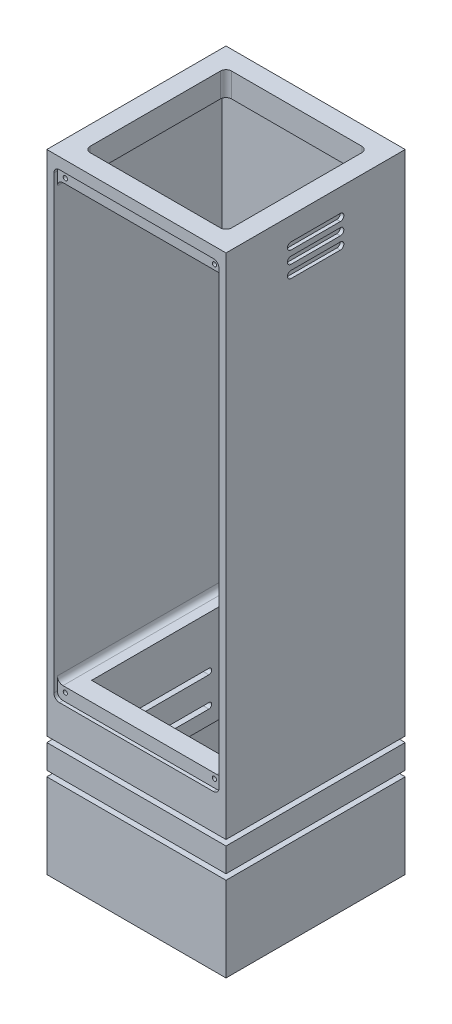
SolidWorks part; units mm, degrees
ref_plane "Front Plane" through (0, 0, 0) normal (0, 0, 1) x (1, 0, 0)
ref_plane "Top Plane" through (0, 0, 0) normal (0, 1, 0) x (1, 0, 0)
ref_plane "Right Plane" through (0, 0, 0) normal (1, 0, 0) x (0, 0, -1)
sketch "Sketch1" plane through (0, 0, 0) normal (0, 1, 0) x (1, 0, 0)
  line L0 (6.35, 44.45) -> (44.45, 44.45)
  line L1 (0, 0) -> (50.8, 0)
  line L2 (0, 0) -> (0, 50.8)
  line L3 (0, 50.8) -> (50.8, 50.8)
  line L4 (50.8, 0) -> (50.8, 50.8)
  line L5 (44.45, 6.35) -> (44.45, 44.45)
  line L6 (6.35, 6.35) -> (44.45, 6.35)
  line L7 (6.35, 6.35) -> (6.35, 44.45)
  dimension "D1" = 50.8
  dimension "D2" = 6.35
extrude "Boss-Extrude1" add sketch "Sketch1" along normal blind 178
sketch "Sketch2" plane through (0, 0, 0) normal (0, -1, 0) x (1, 0, 0)
  line L0 (47.8, -3) -> (3, -3)
  line L1 (3, -3) -> (3, -47.8)
  line L2 (3, -47.8) -> (47.8, -47.8)
  line L3 (47.8, -47.8) -> (47.8, -3)
  line L4 (6.35, -44.45) -> (44.45, -44.45)
  line L5 (6.35, -6.35) -> (6.35, -44.45)
  line L6 (44.45, -6.35) -> (6.35, -6.35)
  line L7 (44.45, -44.45) -> (44.45, -6.35)
  line L8 (6.35, -44.45) -> (44.45, -44.45)
  line L9 (6.35, -6.35) -> (6.35, -44.45)
  line L10 (44.45, -6.35) -> (6.35, -6.35)
  line L11 (44.45, -44.45) -> (44.45, -6.35)
  line L12 (0, -50.8) -> (0, 0) construction
  dimension "D2" = 3
  dimension "D1" = 0
extrude "Cut-Extrude1" cut sketch "Sketch2" against normal blind 20
sketch "Sketch3" plane through (0, 0, 0) normal (0, 0, 1) x (1, 0, 0)
  line L0 (0, 0) -> (50.8, 0) construction
  line L1 (2, 171.15) -> (48.8, 171.15)
  line L2 (2, 171.15) -> (2, 47.675)
  line L3 (2, 47.675) -> (48.8, 47.675)
  line L4 (48.8, 171.15) -> (48.8, 47.675)
  line L5 (0, 178) -> (0, 0) construction
  line L6 (50.8, 178) -> (50.8, 0) construction
  line L7 (0, 178) -> (50.8, 178) construction
  dimension "D1" = 47.675
  dimension "D2" = 2
  dimension "D3" = 2
  dimension "D4" = 6.85
extrude "Cut-Extrude2" cut sketch "Sketch3" against normal blind 47.625
sketch "Sketch4" plane through (0, 0, 0) normal (0, 0, 1) x (1, 0, 0)
  line L0 (0, 178) -> (0, 0) construction
  line L2 (0, 40) -> (0, 24)
  line L3 (0, 24) -> (50.8, 24)
  line L4 (50.8, 40) -> (50.8, 24)
  line L5 (50.8, 178) -> (50.8, 0) construction
  line L6 (0, 0) -> (50.8, 0) construction
  line L10 (0, 40) -> (50.8, 40)
  point P0 (50.8, 39.7289)
  point P10 (0, 39.7848)
  dimension "D1" = 24
  dimension "D2" = 16
extrude "Cut-Extrude3" [suppressed] cut sketch "Sketch4" against normal blind 3.175
sketch "Sketch5" [suppressed] plane through (0, 0, 0) normal (0, 0, 1) x (1, 0, 0)
  line L0 (50.8, 40) -> (0, 40) construction
  line L3 (0, 40) -> (3, 40)
  line L5 (0, 24) -> (50.8, 24) construction
  line L8 (0, 24) -> (3, 24)
  line L10 (0, 40) -> (0, 24)
  line L11 (3, 40) -> (3, 24)
  line L12 (0, 24) -> (0, 0) construction
  point P0 (0, 24)
  dimension "D1" = 3
extrude "Cut-Extrude4" [suppressed] cut sketch "Sketch5" against normal through all
ref_plane "Plane1" through (0, 0, -25.4) normal (0, 0, 1) x (1, 0, 0)
ref_plane "Plane2" through (25.4, 0, 0) normal (-1, 0, 0) x (0, 0, 1)
sketch "Sketch6" plane through (0, 0, 0) normal (-1, 0, 0) x (0, 0, 1)
  line L0 (-32.4, 170.5) -> (-18.4, 170.5) construction
  line L1 (-32.4, 171.5) -> (-18.4, 171.5)
  line L2 (-32.4, 169.5) -> (-18.4, 169.5)
  line L3 (-32.4, 167) -> (-18.4, 167) construction
  line L4 (-32.4, 168) -> (-18.4, 168)
  line L5 (-32.4, 166) -> (-18.4, 166)
  line L6 (-32.4, 163.5) -> (-18.4, 163.5) construction
  line L9 (-32.4, 164.5) -> (-18.4, 164.5)
  line L10 (-32.4, 162.5) -> (-18.4, 162.5)
  line L11 (-25.4, 170.5) -> (-25.4, 167) construction
  line L12 (-25.4, 167) -> (-25.4, 163.5) construction
  line L13 (-25.4, 170.5) -> (-25.4, 178) construction
  line L14 (-50.8, 178) -> (0, 178) construction
  arc A0 (-32.4, 171.5) -> (-32.4, 169.5) centre (-32.4, 170.5) ccw
  arc A1 (-18.4, 169.5) -> (-18.4, 171.5) centre (-18.4, 170.5) ccw
  arc A2 (-32.4, 168) -> (-32.4, 166) centre (-32.4, 167) ccw
  arc A3 (-18.4, 166) -> (-18.4, 168) centre (-18.4, 167) ccw
  arc A6 (-32.4, 164.5) -> (-32.4, 162.5) centre (-32.4, 163.5) ccw
  arc A7 (-18.4, 162.5) -> (-18.4, 164.5) centre (-18.4, 163.5) ccw
  point P2 (-25.4, 170.5)
  point P9 (-25.4, 167)
  point P16 (-25.4, 163.5)
  point P25 (-33.4, 163.5)
  point P26 (-17.4, 163.5)
  dimension "D1" = 3.5
  dimension "D2" = 2
  dimension "D3" = 7.5
  dimension "D4" = 16
extrude "Cut-Extrude5" cut sketch "Sketch6" against normal blind 1
mirror "Mirror1" [suppressed] about plane through (0, 0, -25.4) normal (0, 0, 1)
mirror "Mirror2" about plane through (25.4, 0, 0) normal (-1, 0, 0) of "Cut-Extrude5", "Cut-Extrude4"
sketch "Sketch7" plane through (0, 0, 0) normal (0, 0, 1) x (1, 0, 0)
  line L0 (0, 178) -> (50.8, 178) construction
  line L1 (2, 171.15) -> (48.8, 171.15)
  line L2 (2, 171.15) -> (2, 174.825)
  line L3 (2, 174.825) -> (48.8, 174.825)
  line L4 (48.8, 171.15) -> (48.8, 174.825)
  line L6 (2, 47.675) -> (48.8, 47.675)
  line L7 (2, 47.675) -> (2, 44)
  line L8 (2, 44) -> (48.8, 44)
  line L9 (48.8, 47.675) -> (48.8, 44)
  dimension "D1" = 3.175
extrude "Cut-Extrude6" cut sketch "Sketch7" against normal blind 1
fillet "Fillet1" radius 1.5875 12 edges at (47.8, 10, -47.8) (47.8, 10, -3) (3, 10, -47.8) (3, 10, -3) (48.8, 47.675, -24.3125) (2, 47.675, -24.3125) (48.8, 171.15, -24.3125) (2, 171.15, -24.3125) (48.8, 174.825, -0.5) (2, 174.825, -0.5) (48.8, 44, -0.5) (2, 44, -0.5)
sketch "Sketch8" plane through (0, 178, 0) normal (0, 1, 0) x (1, 0, 0)
  line L1 (6.9375, 45.45) -> (43.8625, 45.45)
  line L2 (5.35, 43.8625) -> (5.35, 6.9375)
  line L3 (6.9375, 5.35) -> (43.8625, 5.35)
  line L4 (45.45, 43.8625) -> (45.45, 6.9375)
  line L8 (6.35, 44.45) -> (6.35, 6.35) construction
  line L10 (6.35, 6.35) -> (44.45, 6.35) construction
  line L11 (44.45, 6.35) -> (44.45, 44.45) construction
  arc A0 (43.8625, 45.45) -> (45.45, 43.8625) centre (43.8625, 43.8625) cw
  arc A1 (45.45, 6.9375) -> (43.8625, 5.35) centre (43.8625, 6.9375) cw
  arc A2 (6.9375, 5.35) -> (5.35, 6.9375) centre (6.9375, 6.9375) cw
  arc A3 (5.35, 43.8625) -> (6.9375, 45.45) centre (6.9375, 43.8625) cw
  dimension "D1" = 1.5875
  dimension "D2" = 1
  dimension "D3" = 1
  dimension "D4" = 1
extrude "Cut-Extrude7" cut sketch "Sketch8" against normal up to next
hole_wizard "#0-80 Tapped Hole1" positions "Sketch12" profile "Sketch14" tap size "#0-80" standard "ANSI Inch"
sketch "Sketch12" plane through (0, 0, -1) normal (0, 0, 1) x (1, 0, 0)
  line L2 (4.2542, 172.571) -> (4.2542, 46.286) construction
  line L3 (4.2542, 46.286) -> (46.5138, 46.286) construction
  line L4 (46.5138, 46.286) -> (46.5138, 172.571) construction
  line L5 (46.5138, 172.571) -> (4.2542, 172.571) construction
  line L8 (0, 178) -> (0, 0) construction
  line L9 (0, 178) -> (50.8, 178) construction
  line L10 (50.8, 178) -> (50.8, 0) construction
  point P0 (4.2542, 172.571)
  point P3 (46.5138, 172.571)
  point P6 (4.2542, 46.286)
  point P9 (46.5138, 46.286)
  point P37 (4.2542, 172.571)
  point P38 (46.5138, 172.571)
  point P39 (4.2542, 46.286)
  dimension "D1" = 4.2542
  dimension "D2" = 5.429
  dimension "D3" = 4.2862
  dimension "D4" = 126.285
sketch "Sketch14" plane through (4.2542, 172.571, -1) normal (1, 0, 0) x (0, -1, 0)
  line L0 (0, 0) -> (0, 3.3576)
  line L1 (0, 3.3576) -> (0.5956, 2.9997)
  line L2 (0.5956, 2.9997) -> (0.5956, 0)
  line L5 (0.5956, 0) -> (0, 0)
  line L10 (0, 3.3576) -> (-0.5956, 2.9997) construction
  line L11 (0, -6.35) -> (0, 107.95) construction
  dimension "Tap Drill Dia." = 1.1913
  dimension "Tap Drill Depth" = 2.9997
  dimension "Drill Angle" = 118
cosmetic thread "Hole Thread5" parameters "D1"=3.048, "D2"=1.524
cosmetic thread "Hole Thread6" parameters "D1"=3.048, "D2"=1.524
cosmetic thread "Hole Thread7" parameters "D1"=3.048, "D2"=1.524
cosmetic thread "Hole Thread8" parameters "D1"=3.048, "D2"=1.524
sketch "Sketch15" [suppressed] plane through (0, 0, -3.175) normal (0, 0, 1) x (1, 0, 0)
  line L0 (11.9875, 32) -> (38.8125, 32) construction
  line L1 (11.9875, 33.5875) -> (38.8125, 33.5875)
  line L2 (11.9875, 30.4125) -> (38.8125, 30.4125)
  line L3 (11.9875, 32) -> (3, 32) construction
  line L4 (3, 24) -> (3, 40) construction
  line L5 (38.8125, 32) -> (47.8, 32) construction
  line L6 (47.8, 24) -> (47.8, 40) construction
  arc A0 (11.9875, 33.5875) -> (11.9875, 30.4125) centre (11.9875, 32) ccw
  arc A1 (38.8125, 30.4125) -> (38.8125, 33.5875) centre (38.8125, 32) ccw
  point P2 (25.4, 32)
  point P15 (25.4, 32)
  point P16 (12.8236, 30.4125)
  point P17 (10.4, 32)
  point P18 (40.4, 32)
  dimension "D1" = 3.175
  dimension "D2" = 30
extrude "Cut-Extrude8" [suppressed] cut sketch "Sketch15" against normal through all
sketch "Sketch16" [suppressed] plane through (3, 0, 0) normal (-1, 0, 0) x (0, 0, 1)
  line L0 (-38.8125, 32) -> (-11.9875, 32) construction
  line L1 (-38.8125, 33.5875) -> (-11.9875, 33.5875)
  line L2 (-38.8125, 30.4125) -> (-11.9875, 30.4125)
  line L3 (-38.8125, 32) -> (-47.625, 32) construction
  line L4 (-47.625, 24) -> (-47.625, 40) construction
  line L5 (-11.9875, 32) -> (-3.175, 32) construction
  line L6 (-3.175, 24) -> (-3.175, 40) construction
  arc A0 (-38.8125, 33.5875) -> (-38.8125, 30.4125) centre (-38.8125, 32) ccw
  arc A1 (-11.9875, 30.4125) -> (-11.9875, 33.5875) centre (-11.9875, 32) ccw
  point P2 (-25.4, 32)
  point P15 (-40.4, 32)
  point P16 (-10.4, 32)
  dimension "D1" = 3.175
  dimension "D2" = 30
extrude "Cut-Extrude9" [suppressed] cut sketch "Sketch16" against normal through all
sketch "Sketch17" [suppressed] plane through (0, 0, -3.175) normal (0, 0, 1) x (1, 0, 0)
  line L0 (3, 24) -> (3, 40) construction
  line L1 (3, 37.0668) -> (47.8, 37.0668)
  line L2 (3, 37.0668) -> (3, 27.0668)
  line L3 (3, 27.0668) -> (47.8, 27.0668)
  line L4 (47.8, 37.0668) -> (47.8, 27.0668)
  line L5 (47.8, 24) -> (47.8, 40) construction
  point P8 (3, 27.0668)
  dimension "D1" = 10
extrude "Cut-Extrude10" [suppressed] cut sketch "Sketch17" against normal blind 0.5
sketch "Sketch18" [suppressed] plane through (0, 0, -3.175) normal (0, 0, 1) x (1, 0, 0)
  line L0 (8.6937, 29) -> (42.1062, 29) construction
  line L1 (8.6937, 29.7938) -> (42.1062, 29.7938)
  line L2 (8.6937, 28.2062) -> (42.1062, 28.2062)
  line L3 (25.4, 29) -> (25.4, 24) construction
  line L4 (0, 24) -> (50.8, 24) construction
  line L5 (8.6937, 35) -> (42.1062, 35) construction
  line L6 (8.6937, 35.7938) -> (42.1062, 35.7938)
  line L7 (8.6937, 34.2063) -> (42.1062, 34.2063)
  line L8 (25.4, 35) -> (25.4, 29) construction
  line L9 (3, 24) -> (47.8, 24) construction
  line L10 (47.8, 40) -> (3, 40) construction
  arc A0 (8.6937, 29.7938) -> (8.6937, 28.2062) centre (8.6937, 29) ccw
  arc A1 (42.1062, 28.2062) -> (42.1062, 29.7938) centre (42.1062, 29) ccw
  arc A2 (8.6937, 35.7938) -> (8.6937, 34.2063) centre (8.6937, 35) ccw
  arc A3 (42.1062, 34.2063) -> (42.1062, 35.7938) centre (42.1062, 35) ccw
  point P2 (25.4, 29)
  point P8 (7.9, 29)
  point P9 (42.9, 29)
  point P13 (9.4875, 35.3192)
  point P16 (25.4, 35)
  point P21 (25.4, 29.0828)
  point P29 (11.625, 34.9125)
  point P30 (11.4537, 29.0875)
  dimension "D1" = 1.5875
  dimension "D2" = 35
  dimension "D3" = 5
  dimension "D4" = 5
extrude "Cut-Extrude11" [suppressed] cut sketch "Sketch18" against normal through all
sketch "Sketch19" plane through (0, 0, 0) normal (0, 0, 1) x (1, 0, 0)
  line L0 (0, 178) -> (0, 0) construction
  line L1 (0, 24) -> (50.8, 24)
  line L2 (0, 24) -> (0, 25.5875)
  line L3 (0, 25.5875) -> (50.8, 25.5875)
  line L4 (50.8, 24) -> (50.8, 25.5875)
  line L5 (50.8, 178) -> (50.8, 0) construction
  line L6 (0, 0) -> (50.8, 0) construction
  point P10 (0, 26.5354)
  point P15 (50.8, 28.4239)
  point P16 (0, 33.0438)
  dimension "D1" = 24
  dimension "D2" = 1.5875
extrude "Cut-Extrude12" cut sketch "Sketch19" against normal blind 4
ref_axis "Axis1" through (25.4, 29.5429, -25.4) along (0, -1, 0)
pattern_circular "CirPattern1" count 4 over 360 about axis through (25.4, 29.5429, -25.4) along (0, -1, 0) of "Cut-Extrude12"
sketch "Sketch20" plane through (46.8, 0, -50.8) normal (-1, 0, 0) x (0, 0, 1)
  line L0 (11.1937, 24.7937) -> (39.6062, 24.7937) construction
  line L1 (11.1937, 25.5875) -> (39.6062, 25.5875)
  line L2 (11.1937, 24) -> (39.6062, 24)
  line L5 (25.4, 24.7937) -> (25.4, 0) construction
  line L7 (46.8, 24) -> (4, 24) construction
  line L8 (0, 25.5875) -> (50.8, 25.5875) construction
  line L10 (50.8, 0) -> (0, 0) construction
  arc A0 (11.1937, 25.5875) -> (11.1937, 24) centre (11.1937, 24.7937) ccw
  arc A1 (39.6062, 24) -> (39.6062, 25.5875) centre (39.6062, 24.7937) ccw
  point P2 (25.4, 24.7937)
  point P13 (10.4, 24.7937)
  point P14 (40.4, 24.7937)
  dimension "D1" = 30
extrude "Cut-Extrude13" cut sketch "Sketch20" along normal through all
pattern_linear "LPattern1" count 2 spacing 8.41 along (0, 1, 0) of "Cut-Extrude12", "Cut-Extrude13", "CirPattern1"
